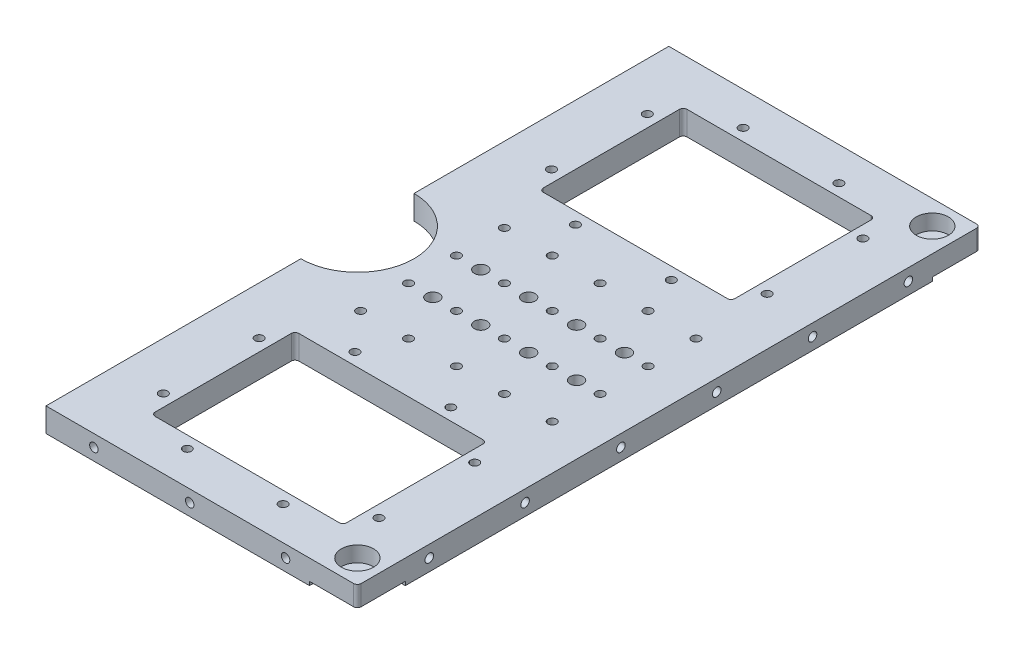
SolidWorks part; units mm, degrees
material "6061 Alloy"
ref_plane "Front Plane" through (0, 0, 0) normal (0, 0, 1) x (1, 0, 0)
ref_plane "Top Plane" through (0, 0, 0) normal (0, 1, 0) x (1, 0, 0)
ref_plane "Right Plane" through (0, 0, 0) normal (1, 0, 0) x (0, 0, -1)
sketch "Sketch1" plane through (0, 0, 0) normal (0, 1, 0) x (1, 0, 0)
  line L0 (0, -15) -> (0, -82.55)
  line L1 (0, 82.55) -> (82.55, 82.55)
  line L2 (0, 82.55) -> (0, 15)
  line L3 (0, -82.55) -> (82.55, -82.55)
  line L4 (82.55, 82.55) -> (82.55, -82.55)
  line L5 (0, 0) -> (82.55, 0) construction
  arc A0 (0, -15) -> (0, 15) centre (0, 0) ccw
  dimension "D1" = 15
  dimension "D2" = 82.55
  dimension "D3" = 165.1
extrude "Boss-Extrude1" add sketch "Sketch1" along normal blind 6.35
hole_wizard "#4-40 Tapped Hole - Z" positions "3DSketch1" profile "Sketch2" tap size "#4-40" standard "ANSI Inch"
sketch3d "3DSketch1"
  line L0 (82.55, 6.35, 82.55) -> (82.55, 6.35, -82.55) construction
  line L2 (82.55, 6.35, 82.55) -> (82.55, 0, 82.55) construction
  point P0 (82.55, 3.175, 63.5)
  dimension "D1" = 3.175
  dimension "D2" = 19.05
sketch "Sketch2" plane through (82.55, 3.175, 63.5) normal (0, 1, 0) x (0, 0, -1)
  line L0 (0, 0) -> (0, 8.2792)
  line L1 (0, 8.2792) -> (1.1303, 7.6)
  line L2 (1.1303, 7.6) -> (1.1303, 0)
  line L5 (1.1303, 0) -> (0, 0)
  line L10 (0, 8.2792) -> (-1.1303, 7.6) construction
  line L11 (0, -6.35) -> (0, 107.95) construction
  dimension "Tap Drill Dia." = 2.2606
  dimension "Tap Drill Depth" = 7.6
  dimension "Drill Angle" = 118
cosmetic thread "Hole Thread1" parameters "D1"=5.69, "D2"=2.8448
pattern_linear "LPattern1" count 6 spacing 25.4 along (0, 0, -1) of "#4-40 Tapped Hole - Z"
cosmetic thread "Hole Thread2" parameters "D1"=5.69, "D2"=2.8448
cosmetic thread "Hole Thread3" parameters "D1"=5.69, "D2"=2.8448
cosmetic thread "Hole Thread4" parameters "D1"=5.69, "D2"=2.8448
cosmetic thread "Hole Thread5" parameters "D1"=5.69, "D2"=2.8448
cosmetic thread "Hole Thread6" parameters "D1"=5.69, "D2"=2.8448
hole_wizard "#4-40 Tapped Hole - X" positions "3DSketch2" profile "Sketch3" tap size "#4-40" standard "ANSI Inch"
sketch3d "3DSketch2"
  line L0 (0, 6.35, 82.55) -> (82.55, 6.35, 82.55) construction
  line L1 (82.55, 6.35, 82.55) -> (82.55, 0, 82.55) construction
  point P0 (63.5, 3.175, 82.55)
  dimension "D1" = 3.175
  dimension "D2" = 19.05
sketch "Sketch3" plane through (63.5, 3.175, 82.55) normal (1, 0, 0) x (0, -1, 0)
  line L0 (0, 0) -> (0, 8.2792)
  line L1 (0, 8.2792) -> (1.1303, 7.6)
  line L2 (1.1303, 7.6) -> (1.1303, 0)
  line L5 (1.1303, 0) -> (0, 0)
  line L10 (0, 8.2792) -> (-1.1303, 7.6) construction
  line L11 (0, -6.35) -> (0, 107.95) construction
  dimension "Tap Drill Dia." = 2.2606
  dimension "Tap Drill Depth" = 7.6
  dimension "Drill Angle" = 118
cosmetic thread "Hole Thread7" parameters "D1"=5.69, "D2"=2.8448
pattern_linear "LPattern2" count 3 spacing 25.4 along (-1, 0, 0) of "#4-40 Tapped Hole - X"
cosmetic thread "Hole Thread8" parameters "D1"=5.69, "D2"=2.8448
cosmetic thread "Hole Thread9" parameters "D1"=5.69, "D2"=2.8448
ref_plane "Plane1" through (0, 0, 0) normal (0, 0, 1) x (1, 0, 0)
mirror "Mirror1" about plane through (0, 0, 0) normal (0, 0, 1) of "LPattern2"
cosmetic thread "Hole Thread10" parameters "D1"=5.69, "D2"=2.8448
cosmetic thread "Hole Thread11" parameters "D1"=5.69, "D2"=2.8448
cosmetic thread "Hole Thread12" parameters "D1"=5.69, "D2"=2.8448
sketch "Cu Flex cable mount dims" plane through (0, 0, 0) normal (0, 1, 0) x (1, 0, 0)
  line L0 (82.55, -82.55) -> (82.55, 82.55) construction
  arc A0 (0, -15) -> (0, 15) centre (0, 0) ccw construction
  point P0 (39.05, 6.35)
  point P1 (64.45, 6.35)
  point P2 (39.05, -6.35)
  point P3 (51.75, 6.35)
  point P4 (64.45, -6.35)
  point P7 (51.75, -6.35)
  point P8 (26.35, 6.35)
  point P9 (26.35, -6.35)
  point P17 (15, 0)
  dimension "D1" = 3
  dimension "D2" = 12.7
  dimension "D3" = 26.35
  dimension "D4" = 12.7
  dimension "D5" = 6.35
  dimension "D6" = 12.7
  dimension "D7" = 18.1
  dimension "D8" = 11.35
sketch "Sketch5" plane through (0, 0, 0) normal (0, 1, 0) x (1, 0, 0)
  line L1 (15.875, 70.5) -> (66.675, 70.5)
  line L2 (15.875, 70.5) -> (15.875, 32.4)
  line L3 (15.875, 32.4) -> (66.675, 32.4)
  line L4 (66.675, 70.5) -> (66.675, 32.4)
  line L9 (0, 82.55) -> (0, 15) construction
  line L10 (82.55, 82.55) -> (0, 82.55) construction
  line L11 (15, 0) -> (82.55, 0) construction
  line L12 (82.55, -82.55) -> (82.55, 82.55) construction
  line L13 (66.675, -70.5) -> (66.675, -32.4)
  line L14 (15.875, -32.4) -> (66.675, -32.4)
  line L15 (15.875, -70.5) -> (15.875, -32.4)
  line L16 (15.875, -70.5) -> (66.675, -70.5)
  arc A0 (0, -15) -> (0, 15) centre (0, 0) ccw construction
  point P8 (28.575, 76.85)
  point P10 (53.975, 76.85)
  point P11 (53.975, 26.05)
  point P12 (28.575, 26.05)
  point P13 (9.525, 51.45)
  point P14 (73.025, 51.45)
  point P15 (28.575, -76.85)
  point P16 (9.525, -51.45)
  point P17 (28.575, -26.05)
  point P18 (53.975, -26.05)
  point P19 (53.975, -76.85)
  point P20 (73.025, -51.45)
  point P21 (15.875, 51.45)
  dimension "D1" = 38.1
  dimension "D2" = 50.8
  dimension "D3" = 15.875
  dimension "D4" = 12.05
  dimension "D5" = 25.4
  dimension "D6" = 12.7
  dimension "D7" = 6.35
  dimension "D8" = 6.35
  dimension "D9" = 6.35
  dimension "D10" = 6.35
extrude "Feedthroughs" cut sketch "Sketch5" along normal up to surface (6.35 mm away) up to face at (30.0167, 6.35, 0)
hole_wizard "#4-40 Tapped Hole - Y" positions "3DSketch5" profile "Sketch7" tap size "#4-40" standard "ANSI Inch" end condition through all
sketch3d "3DSketch5"
  line L0 (66.675, 6.35, -70.5) -> (15.875, 6.35, -70.5) construction
  line L1 (66.675, 6.35, -32.4) -> (66.675, 6.35, -70.5) construction
  line L2 (15.875, 6.35, -32.4) -> (66.675, 6.35, -32.4) construction
  line L3 (15.875, 6.35, -70.5) -> (15.875, 6.35, -32.4) construction
  point P0 (53.975, 6.35, -73.675)
  point P2 (69.85, 6.35, -64.15)
  point P4 (53.975, 6.35, -29.225)
  point P6 (28.575, 6.35, -29.225)
  point P8 (12.7, 6.35, -64.15)
  point P10 (28.575, 6.35, -73.675)
  point P85 (12.7, 6.35, -38.75)
  point P87 (69.85, 6.35, -38.75)
  dimension "D7" = 6.35
  dimension "D4" = 3.175
  dimension "D1" = 25.4
  dimension "D2" = 25.4
  dimension "D3" = 3.175
  dimension "D5" = 3.175
  dimension "D6" = 3.175
  dimension "D8" = 12.7
sketch "Sketch7" plane through (53.975, 6.35, -73.675) normal (1, 0, 0) x (0, 0, 1)
  line L0 (0, 0) -> (0, 6.35)
  line L1 (0, 6.35) -> (1.1303, 6.35)
  line L2 (1.1303, 6.35) -> (1.1303, 0)
  line L5 (1.1303, 0) -> (0, 0)
  line L11 (0, -6.35) -> (0, 107.95) construction
  dimension "Thru Tap Drill Dia." = 2.2606
  dimension "Thru Tap Drill Depth" = 6.35
cosmetic thread "Hole Thread13" parameters "D2"=2.8448
cosmetic thread "Hole Thread14" parameters "D2"=2.8448
cosmetic thread "Hole Thread31" parameters "D2"=2.8448
cosmetic thread "Hole Thread32" parameters "D2"=2.8448
cosmetic thread "Hole Thread33" parameters "D2"=2.8448
cosmetic thread "Hole Thread34" parameters "D2"=2.8448
cosmetic thread "Hole Thread39" parameters "D2"=2.8448
cosmetic thread "Hole Thread40" parameters "D2"=2.8448
mirror "4-40 Tapped Hole - Y Mirror" about plane through (0, 0, 0) normal (0, 0, 1) of "#4-40 Tapped Hole - Y"
cosmetic thread "Hole Thread21" parameters "D2"=2.8448
cosmetic thread "Hole Thread23" parameters "D2"=2.8448
cosmetic thread "Hole Thread35" parameters "D2"=2.8448
cosmetic thread "Hole Thread36" parameters "D2"=2.8448
cosmetic thread "Hole Thread37" parameters "D2"=2.8448
cosmetic thread "Hole Thread38" parameters "D2"=2.8448
cosmetic thread "Hole Thread41" parameters "D2"=2.8448
cosmetic thread "Hole Thread42" parameters "D2"=2.8448
fillet "Fillet1" radius 1 8 edges at (15.875, 3.175, 70.5) (15.875, 3.175, 32.4) (66.675, 3.175, 70.5) (66.675, 3.175, 32.4) (15.875, 3.175, -32.4) (15.875, 3.175, -70.5) (66.675, 3.175, -32.4) (66.675, 3.175, -70.5)
hole_wizard "CBORE for #4 Socket Head Cap Screw1" positions "3DSketch6" profile "Sketch8" counterbore size "#4" standard "ANSI Inch"
sketch3d "3DSketch6"
  line L0 (82.55, 6.35, -82.55) -> (0, 6.35, -82.55) construction
  line L1 (82.55, 6.35, 82.55) -> (82.55, 6.35, -82.55) construction
  line L2 (0, 6.35, 82.55) -> (82.55, 6.35, 82.55) construction
  point P0 (76.2, 6.35, -76.2)
  point P2 (76.2, 6.35, 76.2)
  dimension "D2" = 6.35
  dimension "D1" = 6.35
  dimension "D3" = 6.35
  dimension "D4" = 6.35
sketch "Sketch8" plane through (76.2, 6.35, -76.2) normal (1, 0, 0) x (0, 0, 1)
  line L0 (0, 0) -> (0, 9.8706)
  line L1 (0, 9.8706) -> (1.6319, 8.89)
  line L2 (1.6319, 8.89) -> (1.6319, 4.1148)
  line L3 (1.6319, 4.1148) -> (4.2545, 4.1148)
  line L4 (4.2545, 4.1148) -> (4.2545, 0)
  line L5 (4.2545, 0) -> (0, 0)
  line L10 (0, 9.8706) -> (-1.632, 8.89) construction
  line L11 (0, -6.35) -> (0, 107.95) construction
  dimension "Hole Dia." = 3.2639
  dimension "Hole Depth" = 8.89
  dimension "C'Bore Dia." = 8.509
  dimension "C'Bore Depth" = 4.1148
  dimension "Drill Angle" = 118
hole_wizard "#8-32 Tapped Heat strap" positions "3DSketch7" profile "Sketch9" tap size "#8-32" standard "ANSI Inch" end condition through all
sketch3d "3DSketch7"
  point P0 (26.35, 6.35, -6.35)
  point P2 (39.05, 6.35, -6.35)
  point P4 (51.75, 6.35, -6.35)
  point P6 (64.45, 6.35, -6.35)
  point P8 (64.45, 6.35, 6.35)
  point P10 (51.75, 6.35, 6.35)
  point P12 (39.05, 6.35, 6.35)
  point P14 (26.35, 6.35, 6.35)
sketch "Sketch9" plane through (26.35, 6.35, -6.35) normal (1, 0, 0) x (0, 0, 1)
  line L0 (0, 0) -> (0, 6.35)
  line L1 (0, 6.35) -> (1.7272, 6.35)
  line L2 (1.7272, 6.35) -> (1.7272, 0)
  line L5 (1.7272, 0) -> (0, 0)
  line L11 (0, -6.35) -> (0, 107.95) construction
  dimension "Thru Tap Drill Dia." = 3.4544
  dimension "Thru Tap Drill Depth" = 6.35
cosmetic thread "Hole Thread43" parameters "D2"=4.1656
cosmetic thread "Hole Thread44" parameters "D2"=4.1656
cosmetic thread "Hole Thread45" parameters "D2"=4.1656
cosmetic thread "Hole Thread46" parameters "D2"=4.1656
cosmetic thread "Hole Thread47" parameters "D2"=4.1656
cosmetic thread "Hole Thread48" parameters "D2"=4.1656
cosmetic thread "Hole Thread49" parameters "D2"=4.1656
cosmetic thread "Hole Thread50" parameters "D2"=4.1656
hole_wizard "#4-40 Tapped Grid" positions "3DSketch8" profile "Sketch10" tap size "#4-40" standard "ANSI Inch" end condition through all
sketch3d "3DSketch8"
  line L7 (82.55, 6.35, 82.55) -> (82.55, 6.35, -82.55) construction
  line L8 (16.875, 6.35, -32.4) -> (65.675, 6.35, -32.4) construction
  point P0 (70.7, 6.35, -6.35)
  dimension "D2" = 26.05
  dimension "D1" = 11.85
sketch "Sketch10" plane through (70.7, 6.35, -6.35) normal (1, 0, 0) x (0, 0, 1)
  line L0 (0, 0) -> (0, 6.35)
  line L1 (0, 6.35) -> (1.1303, 6.35)
  line L2 (1.1303, 6.35) -> (1.1303, 0)
  line L5 (1.1303, 0) -> (0, 0)
  line L11 (0, -6.35) -> (0, 107.95) construction
  dimension "Thru Tap Drill Dia." = 2.2606
  dimension "Thru Tap Drill Depth" = 6.35
cosmetic thread "Hole Thread51" parameters "D2"=2.8448
pattern_linear "LPattern4" count 6 spacing 12.7 along (-1, 0, 0) count 3 spacing 12.7 along (0, 0, 1) skipping (5, 0), (5, 1), (5, 2) of "#4-40 Tapped Grid"
cosmetic thread "Hole Thread52" parameters "D2"=2.8448
cosmetic thread "Hole Thread53" parameters "D2"=2.8448
cosmetic thread "Hole Thread54" parameters "D2"=2.8448
cosmetic thread "Hole Thread55" parameters "D2"=2.8448
cosmetic thread "Hole Thread56" parameters "D2"=2.8448
cosmetic thread "Hole Thread57" parameters "D2"=2.8448
cosmetic thread "Hole Thread58" parameters "D2"=2.8448
cosmetic thread "Hole Thread59" parameters "D2"=2.8448
cosmetic thread "Hole Thread60" parameters "D2"=2.8448
cosmetic thread "Hole Thread61" parameters "D2"=2.8448
cosmetic thread "Hole Thread62" parameters "D2"=2.8448
cosmetic thread "Hole Thread63" parameters "D2"=2.8448
cosmetic thread "Hole Thread64" parameters "D2"=2.8448
cosmetic thread "Hole Thread65" parameters "D2"=2.8448
cosmetic thread "Hole Thread66" parameters "D2"=2.8448
cosmetic thread "Hole Thread67" parameters "D2"=2.8448
cosmetic thread "Hole Thread68" parameters "D2"=2.8448
cosmetic thread "Hole Thread69" parameters "D2"=2.8448
cosmetic thread "Hole Thread70" parameters "D2"=2.8448
cosmetic thread "Hole Thread71" parameters "D2"=2.8448
cosmetic thread "Hole Thread72" parameters "D2"=2.8448
cosmetic thread "Hole Thread73" parameters "D2"=2.8448
cosmetic thread "Hole Thread74" parameters "D2"=2.8448
cosmetic thread "Hole Thread75" parameters "D2"=2.8448
cosmetic thread "Hole Thread76" parameters "D2"=2.8448
cosmetic thread "Hole Thread77" parameters "D2"=2.8448
cosmetic thread "Hole Thread78" parameters "D2"=2.8448
cosmetic thread "Hole Thread79" parameters "D2"=2.8448
cosmetic thread "Hole Thread80" parameters "D2"=2.8448
pattern_linear "LPattern5" count 2 spacing 12.7 along (0, 0, -1) count 5 spacing 12.7 along (-1, 0, 0) skipping (0, 1), (0, 2), (0, 3), (0, 4) of "#4-40 Tapped Grid"
cosmetic thread "Hole Thread81" parameters "D2"=2.8448
cosmetic thread "Hole Thread82" parameters "D2"=2.8448
cosmetic thread "Hole Thread83" parameters "D2"=2.8448
cosmetic thread "Hole Thread84" parameters "D2"=2.8448
cosmetic thread "Hole Thread85" parameters "D2"=2.8448
sketch "Bar_cutouts" plane through (0, 0, 0) normal (0, 1, 0) x (1, 0, 0)
  line L0 (69.85, 82.55) -> (69.85, 69.85)
  line L1 (82.55, 82.55) -> (0, 82.55) construction
  line L2 (69.85, 69.85) -> (82.55, 69.85)
  line L3 (82.55, -82.55) -> (82.55, 82.55) construction
  line L4 (69.85, 82.55) -> (82.55, 82.55)
  line L5 (82.55, 82.55) -> (82.55, 69.85)
  line L6 (0, 0) -> (82.55, 0) construction
  line L7 (82.55, -82.55) -> (82.55, -69.85)
  line L8 (69.85, -82.55) -> (82.55, -82.55)
  line L9 (69.85, -82.55) -> (69.85, -69.85)
  line L10 (69.85, -69.85) -> (82.55, -69.85)
  circle A0 centre (69.85, 69.85) radius 1
  circle A1 centre (69.85, -69.85) radius 1
  dimension "D2" = 2
  dimension "D1" = 12.7
extrude "Cut-Extrude1" cut sketch "Bar_cutouts" along normal blind 1 contours A0 L2 L5 L4 L0 | L0 A0 L2 | A1 L9 L10 | L10 A1 L9 L8 L7 | L2 A0 L0 | A1 L10 L9 region at (76.229, 0, -76.229) region at (70.2744, 0, -70.2744) region at (69.7085, 0, -69.7085) region at (76.229, 0, 76.229) region at (70.2744, 0, 70.2744) region at (69.7085, 0, 69.7085)
fillet "Fillet2" radius 1 2 edges at (82.55, 3.675, -82.55) (82.55, 3.675, 82.55)
equation "\"Width\"=82.55"
equation "\"D2@Sketch1\"=\"Width\""
equation "\"D3@Sketch5\"=(\"Width\"-\"D2@Sketch5\")/2"
equation "\"D4@Sketch5\"=(62.2-\"D1@Sketch5\")/2"
equation "\"D8@Sketch5\"=\"D7@Sketch5\""
equation "\"D9@Sketch5\"=\"D7@Sketch5\""
equation "\"D10@Sketch5\"=\"D9@Sketch5\""
equation "\"D2@3DSketch6\"=\"D1@3DSketch6\""
equation "\"D4@3DSketch6\"=\"D3@3DSketch6\""
equation "\"D4@3DSketch5\"=\"D3@3DSketch5\""
equation "\"D5@3DSketch5\"=\"D3@3DSketch5\""
equation "\"D6@3DSketch5\"=\"D3@3DSketch5\""
equation "\"D7@3DSketch5\"=(38.1-\"D2@3DSketch5\")/2"
equation "\"D8@3DSketch5\"=(50.8-\"D1@3DSketch5\")/2"
